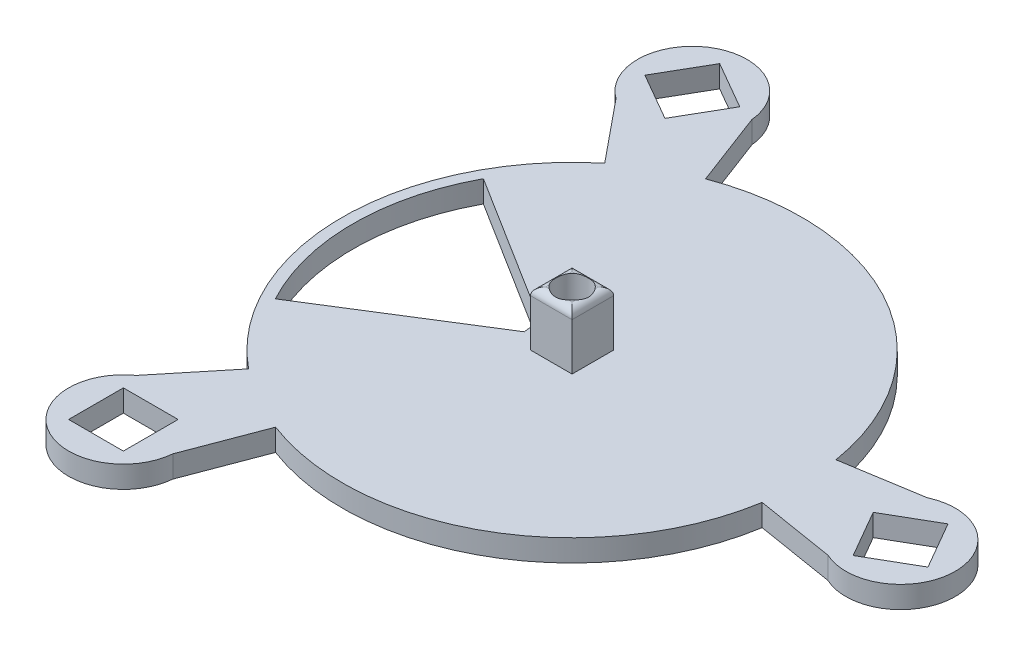
SolidWorks part; units mm, degrees
ref_plane "Front Plane" through (0, 0, 0) normal (0, 0, 1) x (1, 0, 0)
ref_plane "Top Plane" through (0, 0, 0) normal (0, 1, 0) x (1, 0, 0)
ref_plane "Right Plane" through (0, 0, 0) normal (1, 0, 0) x (0, 0, -1)
sketch "Sketch1" plane through (0, 0, 0) normal (0, 1, 0) x (1, 0, 0)
  line L0 (0, 0) -> (-15, -25.9808) construction
  line L4 (-17.5, -23.4808) -> (-12.5, -23.4808)
  line L5 (-17.5, -23.4808) -> (-17.5, -28.4808)
  line L6 (-17.5, -28.4808) -> (-12.5, -28.4808)
  line L7 (-12.5, -23.4808) -> (-12.5, -28.4808)
  line L8 (0, 0) -> (-17.8866, -21.8982)
  line L15 (0, 0) -> (-10.0211, -26.4394)
  line L16 (-11.5849, 26.8958) -> (-14.0849, 22.5657)
  line L17 (-11.5849, 26.8958) -> (-15.9151, 29.3958)
  line L18 (-15.9151, 29.3958) -> (-18.4151, 25.0657)
  line L19 (-14.0849, 22.5657) -> (-18.4151, 25.0657)
  line L20 (0, 0) -> (-10.0211, 26.4394)
  line L21 (0, 0) -> (-15, 25.9808) construction
  line L22 (0, 0) -> (-17.8866, 21.8982)
  line L23 (29.0849, -3.4151) -> (26.5849, 0.9151)
  line L24 (29.0849, -3.4151) -> (33.4151, -0.9151)
  line L25 (33.4151, -0.9151) -> (30.9151, 3.4151)
  line L26 (26.5849, 0.9151) -> (30.9151, 3.4151)
  line L27 (0, 0) -> (27.9077, -4.5412)
  line L28 (0, 0) -> (30, 0) construction
  line L29 (0, 0) -> (27.9077, 4.5412)
  line L30 (0, 0) -> (0, -21) construction
  circle A0 centre (0, 0) radius 21
  arc A1 (-17.8866, -21.8982) -> (-10.0211, -26.4394) centre (-15, -25.9808) ccw
  arc A2 (-10.0211, 26.4394) -> (-17.8866, 21.8982) centre (-15, 25.9808) ccw
  arc A3 (27.9077, -4.5412) -> (27.9077, 4.5412) centre (30, 0) ccw
  point P8 (-15, -28.4808)
  point P9 (-17.5, -25.9808)
  point P29 (0, 0)
  dimension "D1" = 42
  dimension "D5" = 5
  dimension "D2" = 30
  dimension "D3" = 5
  dimension "D4" = 28.2748
  dimension "D6" = 3
  dimension "D7" = 120
  dimension "D8" = 120
  dimension "D9" = 120
  dimension "D10" = 30
extrude "Boss-Extrude1" add sketch "Sketch1" along normal blind 2 contours L8 A1 L15 A0 L4 L7 L6 L5 | L27 A3 L29 A0 L23 L26 L25 L24 | L20 A2 L22 A0 L16 L19 L18 L17 | A0 region at (-10.5967, 0, 18.3541) region at (-10.5967, 0, -18.3541) region at (21.1054, 0, 1.7059)
ref_plane "Plane1" through (0, 2, 0) normal (0, 1, 0) x (1, 0, 0)
sketch "Sketch2" plane through (0, 2, 0) normal (0, 1, 0) x (1, 0, 0)
  line L1 (-1.9, 1.9) -> (1.9, 1.9)
  line L2 (-1.9, 1.9) -> (-1.9, -1.9)
  line L3 (-1.9, -1.9) -> (1.9, -1.9)
  line L4 (1.9, 1.9) -> (1.9, -1.9)
  point P4 (0, -1.9)
  point P6 (-1.9, 0)
  dimension "D1" = 3.8
extrude "Boss-Extrude2" add sketch "Sketch2" along normal blind 5
ref_plane "Plane2" through (0, 7, 0) normal (0, 1, 0) x (1, 0, 0)
sketch "Sketch3" plane through (0, 7, 0) normal (0, 1, 0) x (1, 0, 0)
  circle A0 centre (0, 0) radius 1.5
  dimension "D1" = 3
extrude "Cut-Extrude1" cut sketch "Sketch3" against normal up to next
sketch "Sketch4" plane through (0, 2, 0) normal (0, 1, 0) x (1, 0, 0)
  line L0 (0, 0) -> (-20, 0) construction
  line L1 (-3.6203, -0.735) -> (-17.5997, -9.5)
  line L2 (-3.6203, 0.735) -> (-17.5997, 9.5)
  arc A1 (-17.5997, 9.5) -> (-17.5997, -9.5) centre (0, 0) ccw
  arc A2 (-3.6203, 0.735) -> (-3.6203, -0.735) centre (0, 0) ccw
  dimension "D1" = 40
  dimension "D4" = 1.47
  dimension "D2" = 9.5
  dimension "D3" = 9.5
  dimension "D5" = 16.5
extrude "Cut-Extrude2" cut sketch "Sketch4" against normal up to next
fillet "Fillet1" radius 0.7 4 edges at (1.9, 7, 0) (0, 7, -1.9) (-1.9, 7, 0) (0, 7, 1.9)
